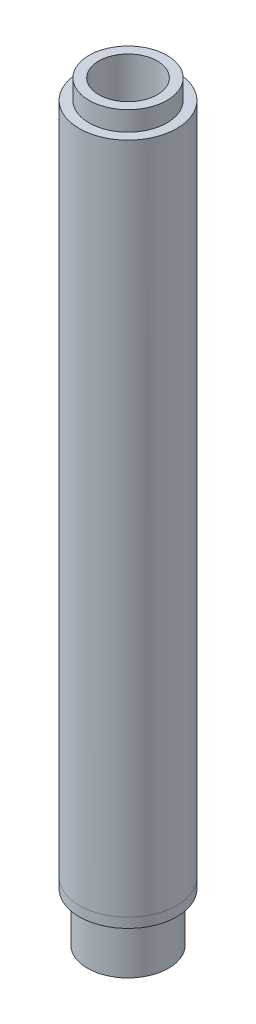
SolidWorks part; units mm, degrees
ref_plane "Front Plane" through (0, 0, 0) normal (0, 0, 1) x (1, 0, 0)
ref_plane "Top Plane" through (0, 0, 0) normal (0, 1, 0) x (1, 0, 0)
ref_plane "Right Plane" through (0, 0, 0) normal (1, 0, 0) x (0, 0, -1)
sketch "Sketch1" plane through (0, 0, 0) normal (0, 1, 0) x (1, 0, 0)
  circle A0 centre (0, 0) radius 12.7
  dimension "D1" = 25.4
extrude "Boss-Extrude1" add sketch "Sketch1" along normal blind 177.8
sketch "Sketch4" plane through (0, 177.8, 0) normal (0, 1, 0) x (1, 0, 0)
  circle A2 centre (0, 0) radius 10.16
  circle A3 centre (0, 0) radius 10.16
  dimension "D1" = 2.54
extrude "Boss-Extrude2" add sketch "Sketch4" along normal blind 5.08
sketch "Sketch5" plane through (0, 182.88, 0) normal (0, 1, 0) x (1, 0, 0)
  circle A0 centre (0, 0) radius 10.16 construction
  circle A1 centre (0, 0) radius 10.16 construction
  circle A2 centre (0, 0) radius 7.62
  dimension "D1" = 2.54
extrude "Cut-Extrude1" cut sketch "Sketch5" against normal through all
sketch "Sketch6" plane through (0, 0, 0) normal (0, -1, 0) x (1, 0, 0)
  circle A0 centre (0, 0) radius 10.541
  circle A1 centre (0, 0) radius 7.62 construction
  circle A2 centre (0, 0) radius 7.62
  dimension "D1" = 21.082
extrude "Boss-Extrude3" add sketch "Sketch6" along normal blind 12.7
sketch "Sketch7" plane through (0, -12.7, 0) normal (0, -1, 0) x (1, 0, 0)
  circle A0 centre (0, 0) radius 12.7 construction
  circle A1 centre (0, 0) radius 12.7
sketch "Sketch8" plane through (0, 182.88, 0) normal (0, 1, 0) x (1, 0, 0)
  circle A0 centre (0, 0) radius 12.7 construction
  circle A1 centre (0, 0) radius 12.7
ref_plane "Plane1" through (0, 2.54, 0) normal (0, -1, 0) x (-1, 0, 0)
split "Split1" trim tools "Plane1" bodies to split 104 resulting bodies 110 111
